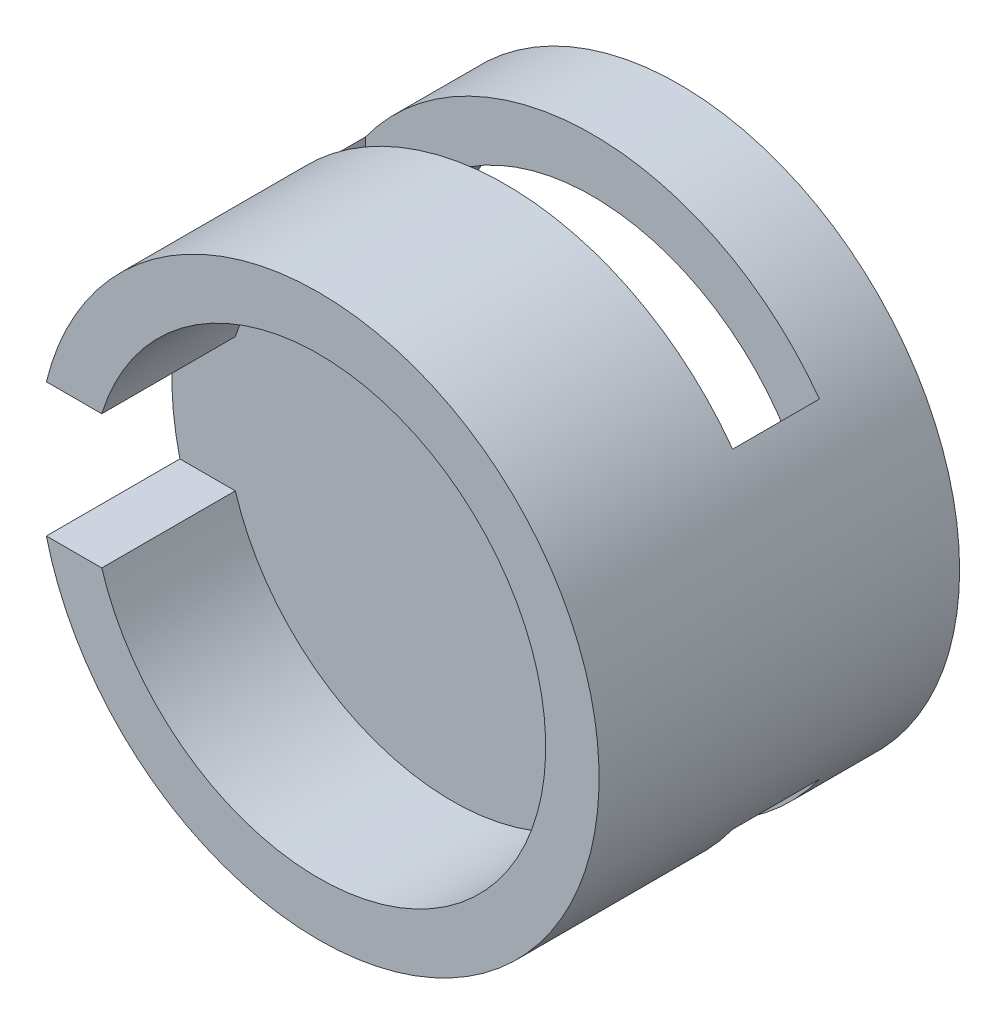
SolidWorks part; units mm, degrees
ref_plane "Plano frontal" through (0, 0, 0) normal (0, 0, 1) x (1, 0, 0)
ref_plane "Plano superior" through (0, 0, 0) normal (0, 1, 0) x (1, 0, 0)
ref_plane "Plano direito" through (0, 0, 0) normal (1, 0, 0) x (0, 0, -1)
sketch "Esboço1" plane through (0, 0, 0) normal (0, 0, 1) x (1, 0, 0)
  circle A0 centre (0, 0) radius 17
  circle A1 centre (0, 0) radius 21
extrude "Ressalto-extrusão1" add sketch "Esboço1" along normal blind 10
sketch "Esboço2" plane through (0, 0, 0) normal (0, 0, -1) x (-1, 0, 0)
  circle A1 centre (0, 0) radius 21
  circle A2 centre (0, 0) radius 21
  dimension "D1" = 0
extrude "Ressalto-extrusão2" add sketch "Esboço2" along normal blind 4
sketch "Esboço3" plane through (0, 0, 10) normal (0, 0, 1) x (1, 0, 0)
  line L1 (-28.8516, 5) -> (-13.1484, 5)
  line L2 (-28.8516, 5) -> (-28.8516, -5)
  line L3 (-28.8516, -5) -> (-13.1484, -5)
  line L4 (-13.1484, 5) -> (-13.1484, -5)
  line L5 (-28.8516, 5) -> (-13.1484, -5) construction
  line L6 (-28.8516, -5) -> (-13.1484, 5) construction
  circle A0 centre (0, 0) radius 21 construction
  point P0 (-21, 0)
extrude "Corte-extrusão1" cut sketch "Esboço3" against normal up to surface (10 mm away) up to face at (17, 0, 0)
sketch "Esboço8" plane through (0, 0, 0) normal (0, 0, 1) x (1, 0, 0)
  circle A0 centre (0, 0) radius 17
  circle A1 centre (0, 0) radius 21
extrude "Ressalto-extrusão4" add sketch "Esboço8" against normal blind 17
sketch "Esboço12" plane through (0, 0, 0) normal (0, 1, 0) x (1, 0, 0)
  line L0 (17, 4) -> (17, 17) construction
  line L1 (-17, 4) -> (17, 4)
  line L2 (-17, 4) -> (-17, 10.5)
  line L3 (-17, 10.5) -> (17, 10.5)
  line L4 (17, 4) -> (17, 10.5)
extrude "Corte-extrusão3" cut sketch "Esboço12" against normal blind 27 and the other way blind 27
sketch "Esboço13" plane through (0, 0, 0) normal (1, 0, 0) x (0, 0, -1)
  line L0 (-10, 0) -> (-162.4, 0) construction
  line L1 (-10, 21) -> (-10, -21) construction
